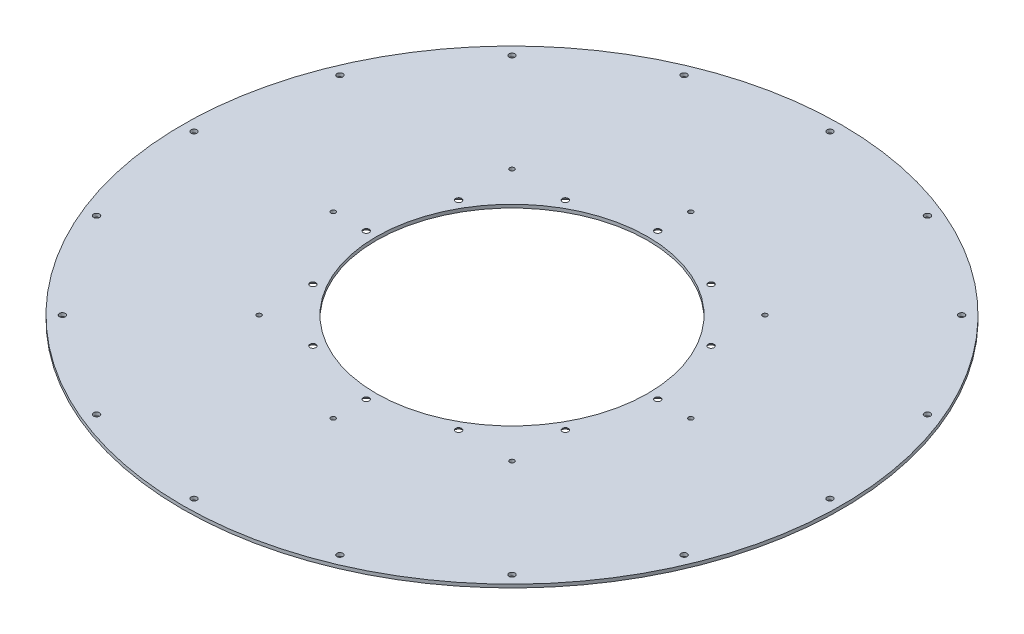
SolidWorks part; units mm, degrees
material "ASTM A36 Steel"
ref_plane "Front Plane" through (0, 0, 0) normal (0, 0, 1) x (1, 0, 0)
ref_plane "Top Plane" through (0, 0, 0) normal (0, 1, 0) x (1, 0, 0)
ref_plane "Right Plane" through (0, 0, 0) normal (1, 0, 0) x (0, 0, -1)
sketch "Sketch1" plane through (0, 0, 0) normal (0, 1, 0) x (1, 0, 0)
  circle A0 centre (0, 0) radius 497.5
  circle A1 centre (0, 0) radius 205
  dimension "D1" = 995
  dimension "D2" = 410
extrude "Boss-Extrude1" add sketch "Sketch1" along normal blind 5
sketch "Sketch2" plane through (0, 5, 0) normal (0, 1, 0) x (1, 0, 0)
  line L0 (0, 0) -> (0, 353.8049) construction
  circle A0 centre (0, 0) radius 480 construction
  circle A1 centre (0, 480) radius 4.5
  circle A2 centre (0, 0) radius 270 construction
  circle A3 centre (0, 270) radius 3.5
  dimension "D1" = 960
  dimension "D2" = 540
  dimension "D4" = 9
  dimension "D5" = 7
extrude "Cut-Extrude1" cut sketch "Sketch2" against normal blind 10 contours A0 A1 L0 | L0 A1 A0 | A0 A1 L0 | L0 A1 A0 | L0 | L0 | L0 | L0 | A2 A3 L0 | L0 A3 A2 | A2 A3 L0 | L0 A3 A2 region at (0, 5, -480) region at (0, 5, -270)
pattern_circular "CirPattern1" count 16 over 360 about axis through (0, 5, 0) along (0, 1, 0) of face at (0, 5, -475.5)
pattern_circular "CirPattern2" count 8 over 360 about axis through (0, 5, 0) along (0, 1, 0) of face at (0, 5, -266.5)
sketch "Sketch3" plane through (0, 5, 0) normal (0, 1, 0) x (1, 0, 0)
  circle A0 centre (0, 0) radius 220 construction
  circle A1 centre (0, 220) radius 4.5
  dimension "D1" = 9
  dimension "D2" = 440
  dimension "D3" = 220
extrude "Cut-Extrude3" cut sketch "Sketch3" against normal blind 10 draft 40 draft outward yes
pattern_circular "CirPattern3" count 12 over 360 about axis through (0, 5, 0) along (0, 1, 0) of "Cut-Extrude3"
